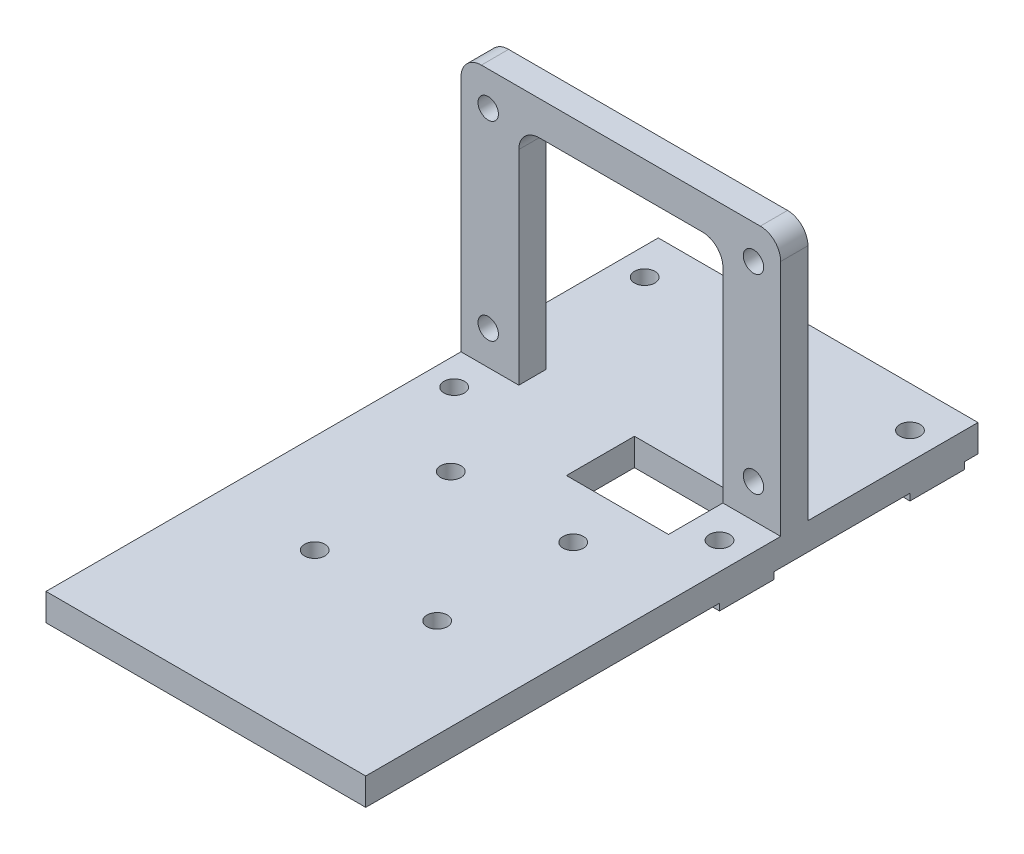
SolidWorks part; units mm, degrees
material "聚脂树脂"
ref_plane "前视基准面" through (0, 0, 0) normal (0, 0, 1) x (1, 0, 0)
ref_plane "上视基准面" through (0, 0, 0) normal (0, 1, 0) x (1, 0, 0)
ref_plane "右视基准面" through (0, 0, 0) normal (1, 0, 0) x (0, 0, -1)
other "Configuration Table"
sketch "草图1" plane through (0, 0, 0) normal (0, 1, 0) x (1, 0, 0)
  line L0 (0, 0) -> (0, 40.9092) construction
  line L1 (-23.5, -20) -> (23.5, -20)
  line L2 (-23.5, -20) -> (-23.5, 20)
  line L3 (-23.5, 20) -> (23.5, 20)
  line L4 (23.5, -20) -> (23.5, 20)
  line L5 (-23.5, -20) -> (23.5, 20) construction
  line L6 (-23.5, 20) -> (23.5, -20) construction
  line L7 (0, 0) -> (66.2179, 0) construction
  line L16 (0, 0) -> (0, -21.1131) construction
  line L17 (-15, -7) -> (15, -7)
  line L18 (15, -7) -> (15, -17)
  line L19 (15, -17) -> (-15, -17)
  line L20 (-15, -7) -> (-15, -17)
  line L21 (-23.5, -20) -> (-23.5, -70)
  line L22 (-23.5, -70) -> (23.5, -70)
  line L23 (23.5, -70) -> (23.5, -20)
  line L24 (0, -7) -> (0, -17)
  circle A0 centre (19.5, 14) radius 1.5
  circle A1 centre (19.5, -14) radius 1.5
  circle A2 centre (-19.5, -14) radius 1.5
  circle A3 centre (-19.5, 14) radius 1.5
  point P0 (0, 0)
  point P23 (0, -17)
  point P24 (0, -7)
  dimension "D3" = 3
  dimension "D4" = 39
  dimension "D5" = 28
  dimension "D1" = 47
  dimension "D2" = 40
  dimension "D6" = 30
  dimension "D7" = 10
  dimension "D8" = 7
  dimension "D9" = 70
extrude "凸台-拉伸1" add sketch "草图1" along normal blind 4 contours L1 L4 L3 L2 A1 A0 L20 L17 L18 L19 A2 A3 | L22 L23 L1 L21 | L24 L17 L20 L19 region at (0, 0, -2.32) region at (0, 0, 45) region at (-7.5, 0, 12)
sketch "草图3" plane through (0, 0, 0) normal (0, -1, 0) x (1, 0, 0)
  line L0 (0, 0) -> (41.6004, 0) construction
  line L5 (15.5, -18) -> (23.5, -18)
  line L6 (15.5, 10) -> (23.5, 10)
  line L7 (0, 0) -> (0, 32.2448) construction
  line L16 (15.5, 10) -> (15.5, 18)
  line L17 (15.5, 18) -> (23.5, 18)
  line L22 (23.5, 10) -> (23.5, 18)
  line L23 (15.5, 10) -> (23.5, 18) construction
  line L24 (15.5, 18) -> (23.5, 10) construction
  line L25 (23.5, -10) -> (23.5, -18)
  line L26 (15.5, -10) -> (23.5, -10)
  line L27 (15.5, -10) -> (15.5, -18)
  line L28 (-15.5, -10) -> (-15.5, -18)
  line L29 (-15.5, -10) -> (-23.5, -10)
  line L30 (-23.5, -10) -> (-23.5, -18)
  line L31 (-15.5, -18) -> (-23.5, -18)
  line L32 (-15.5, 18) -> (-23.5, 18)
  line L33 (-23.5, 10) -> (-23.5, 18)
  line L34 (-15.5, 10) -> (-23.5, 10)
  line L35 (-15.5, 10) -> (-15.5, 18)
  circle A8 centre (-19.5, 14) radius 1.5 construction
  circle A9 centre (-19.5, -14) radius 1.5 construction
  circle A10 centre (19.5, -14) radius 1.5 construction
  circle A11 centre (19.5, 14) radius 1.5 construction
  circle A12 centre (-19.5, 14) radius 1.5
  circle A13 centre (-19.5, -14) radius 1.5
  circle A14 centre (19.5, -14) radius 1.5
  circle A15 centre (19.5, 14) radius 1.5
  point P0 (19.5, 14)
  point P22 (-19.5, 14)
  dimension "D1" = 8
  dimension "D2" = 8
extrude "凸台-拉伸2" add sketch "草图3" along normal blind 1
sketch "草图4" plane through (0, 4, 0) normal (0, 1, 0) x (1, 0, 0)
  line L0 (0, 0) -> (0, -72.3063) construction
  line L1 (-23.5, -70) -> (23.5, -70) construction
  circle A0 centre (9, -25) radius 1.5
  circle A1 centre (9, -45) radius 1.5
  circle A2 centre (-9, -45) radius 1.5
  circle A3 centre (-9, -25) radius 1.5
  dimension "D1" = 3
  dimension "D2" = 3
  dimension "D3" = 20
  dimension "D4" = 18
  dimension "D5" = 25
  dimension "D6" = 18
extrude "切除-拉伸2" cut sketch "草图4" against normal blind 4
sketch "草图5" plane through (0, 4, 0) normal (0, 1, 0) x (1, 0, 0)
  line L0 (0, -5) -> (0, 34.0121) construction
  line L1 (0, -5) -> (39.4094, -5) construction
  line L2 (15, -5) -> (23.5, -5)
  line L3 (23.5, -70) -> (23.5, 20) construction
  line L4 (23.5, -5) -> (23.5, -9)
  line L5 (23.5, -9) -> (15, -9)
  line L6 (15, -9) -> (15, -5)
  line L7 (-23.5, -9) -> (-15, -9)
  line L8 (-23.5, -5) -> (-23.5, -9)
  line L9 (-15, -5) -> (-23.5, -5)
  line L10 (-15, -9) -> (-15, -5)
  line L11 (0, 0) -> (38.2779, 0) construction
  line L12 (0, 0) -> (0, 10.5962) construction
  dimension "D1" = 30
  dimension "D2" = 5
  dimension "D3" = 4
extrude "凸台-拉伸3" add sketch "草图5" along normal blind 38
sketch "草图6" plane through (0, 0, 9) normal (0, 0, 1) x (1, 0, 0)
  line L0 (0, 0) -> (0, 41.5452) construction
  line L1 (0, 23) -> (26.2414, 23) construction
  line L2 (-23.5, 4) -> (23.5, 4) construction
  circle A0 centre (19.5, 37) radius 1.5
  circle A1 centre (19.5, 9) radius 1.5
  circle A2 centre (-19.5, 9) radius 1.5
  circle A3 centre (-19.5, 37) radius 1.5
  dimension "D1" = 3
  dimension "D2" = 28
  dimension "D3" = 39
  dimension "D4" = 19
extrude "切除-拉伸3" cut sketch "草图6" against normal blind 10
sketch "草图7" plane through (0, 0, 9) normal (0, 0, 1) x (1, 0, 0)
  line L0 (-15, 42) -> (15, 42)
  line L1 (15, 42) -> (15, 37)
  line L2 (15, 42) -> (15, 4) construction
  line L3 (15, 37) -> (-15, 37)
  line L4 (-15, 42) -> (-15, 4) construction
  line L5 (-15, 37) -> (-15, 42)
  dimension "D1" = 5
extrude "凸台-拉伸4" add sketch "草图7" against normal blind 4
fillet "圆角1" radius 3 4 edges at (-23.5, 42, 7) (23.5, 42, 7) (15, 37, 7) (-15, 37, 7)
